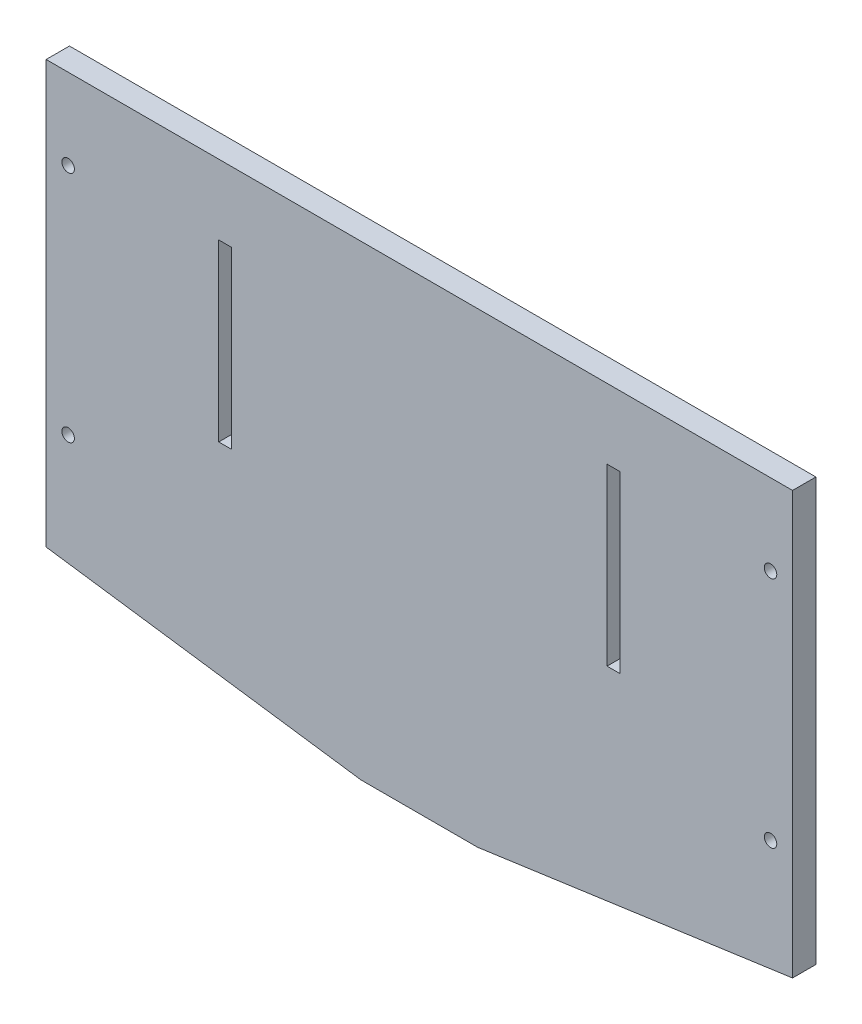
SolidWorks part; units mm, degrees
material "Acrylic (Medium-high impact)"
ref_plane "Front Plane" through (0, 0, 0) normal (0, 0, 1) x (1, 0, 0)
ref_plane "Top Plane" through (0, 0, 0) normal (0, 1, 0) x (1, 0, 0)
ref_plane "Right Plane" through (0, 0, 0) normal (1, 0, 0) x (0, 0, -1)
sketch "Sketch1" plane through (0, 0, 0) normal (0, 0, 1) x (1, 0, 0)
  line L1 (203.2, 127) -> (0, 127)
  line L2 (203.2, 127) -> (203.2, 0)
  line L3 (203.2, 0) -> (0, 0)
  line L4 (0, 127) -> (0, 0)
  line L5 (203.2, 127) -> (0, 0) construction
  line L6 (203.2, 0) -> (0, 127) construction
  point P0 (101.6, 63.5)
  dimension "D1" = 127
  dimension "D2" = 203.2
extrude "Boss-Extrude1" add sketch "Sketch1" along normal blind 6.35
hole_wizard "M3 Clearance Hole1" positions "Sketch2" profile "Sketch3" hole size "M3" standard "ANSI Metric" end condition through all
sketch "Sketch2" plane through (0, 0, 6.35) normal (0, 0, 1) x (1, 0, 0)
  line L0 (0, 127) -> (0, 0) construction
  line L1 (203.2, 127) -> (0, 127) construction
  line L2 (203.2, 0) -> (203.2, 127) construction
  point P0 (5.9944, 105.0036)
  point P2 (5.9944, 41.5036)
  point P4 (197.2056, 41.5036)
  point P6 (197.2056, 105.0036)
  dimension "D1" = 5.9944
  dimension "D2" = 21.9964
  dimension "D3" = 5.9944
  dimension "D4" = 63.5
sketch "Sketch3" plane through (5.9944, 105.0036, 6.35) normal (1, 0, 0) x (0, -1, 0)
  line L0 (0, 0) -> (0, 6.35)
  line L1 (0, 6.35) -> (1.7, 6.35)
  line L2 (1.7, 6.35) -> (1.7, 0)
  line L5 (1.7, 0) -> (0, 0)
  line L11 (0, -6.35) -> (0, 107.95) construction
  dimension "Thru Hole Dia." = 3.4
  dimension "Thru Hole Depth" = 6.35
sketch "Sketch4" plane through (0, 0, 6.35) normal (0, 0, 1) x (1, 0, 0)
  line L0 (0, 127) -> (0, 0) construction
  line L1 (46.99, 107.95) -> (50.4952, 107.95)
  line L2 (46.99, 107.95) -> (46.99, 60.325)
  line L3 (46.99, 60.325) -> (50.4952, 60.325)
  line L4 (50.4952, 107.95) -> (50.4952, 60.325)
  line L5 (152.7048, 107.95) -> (156.21, 107.95)
  line L6 (152.7048, 107.95) -> (152.7048, 60.325)
  line L7 (152.7048, 60.325) -> (156.21, 60.325)
  line L8 (156.21, 107.95) -> (156.21, 60.325)
  line L9 (203.2, 0) -> (203.2, 127) construction
  line L10 (203.2, 127) -> (0, 127) construction
  dimension "D1" = 3.5052
  dimension "D2" = 47.625
  dimension "D3" = 46.99
  dimension "D4" = 46.99
  dimension "D5" = 19.05
extrude "Cut-Extrude1" cut sketch "Sketch4" against normal through all
sketch "Sketch5" plane through (0, 0, 6.35) normal (0, 0, 1) x (1, 0, 0)
  line L0 (0, 12.0479) -> (85.725, 0)
  line L1 (0, 127) -> (0, 0) construction
  line L2 (0, 0) -> (203.2, 0) construction
  line L3 (85.725, 0) -> (0, 0)
  line L4 (0, 0) -> (0, 12.0479)
  line L5 (117.475, 0) -> (203.2, 0)
  line L6 (203.2, 0) -> (203.2, 12.0479)
  line L7 (203.2, 0) -> (203.2, 127) construction
  line L8 (203.2, 12.0479) -> (117.475, 0)
  dimension "D1" = 8
  dimension "D2" = 8
  dimension "D3" = 31.75
extrude "Cut-Extrude2" cut sketch "Sketch5" against normal through all
